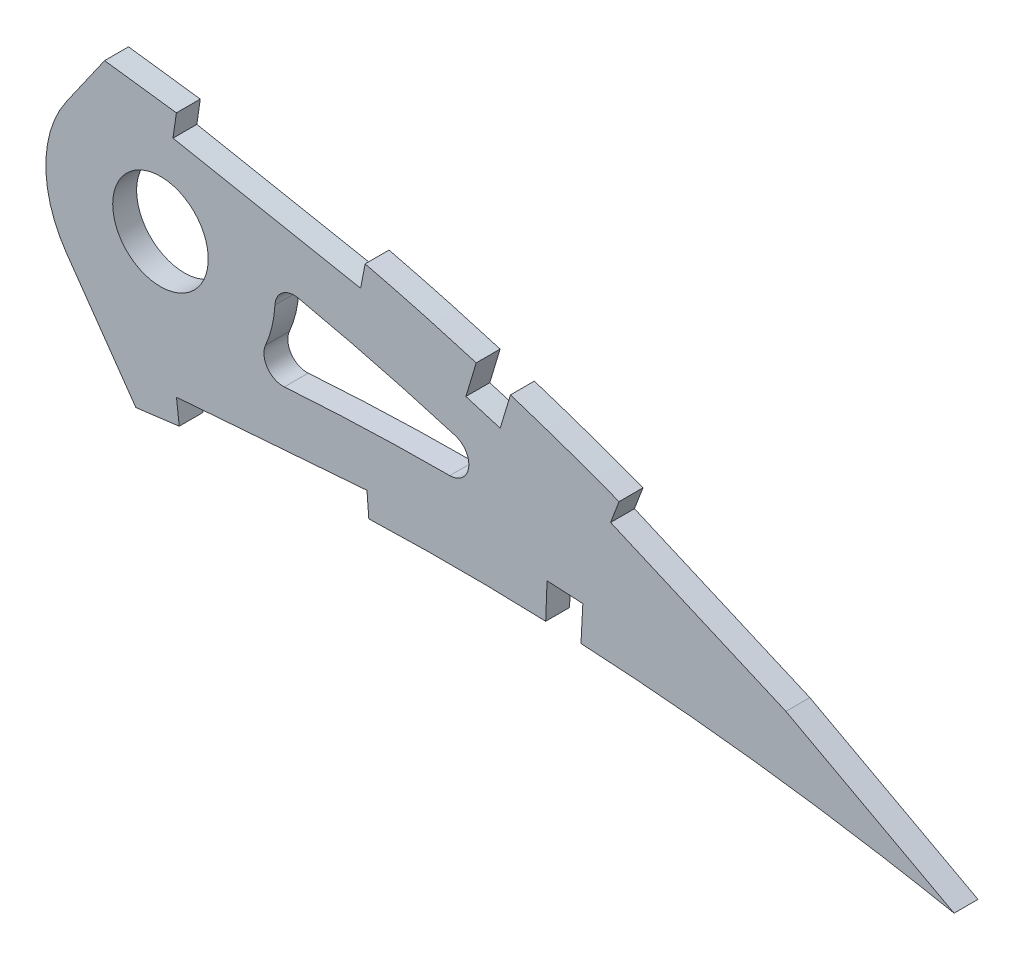
SolidWorks part; units mm, degrees
ref_plane "Front Plane" through (0, 0, 0) normal (0, 0, 1) x (1, 0, 0)
ref_plane "Top Plane" through (0, 0, 0) normal (0, 1, 0) x (1, 0, 0)
ref_plane "Right Plane" through (0, 0, 0) normal (1, 0, 0) x (0, 0, -1)
curve "Curve1"
  spline degree 3 poles (383.949, 0.5986, 0) (383.9196, 0.6168, 0) (383.802, 0.6894, 0) (383.5372, 0.8518, 0) (383.0962, 1.1224, 0) (382.4788, 1.4992, 0) (381.6856, 1.9812, 0) (380.716, 2.5651, 0) (379.5708, 3.249, 0) (378.2502, 4.0295, 0) (376.7543, 4.9032, 0) (375.0838, 5.8664, 0) (373.2387, 6.9137, 0) (371.2197, 8.0407, 0) (369.0276, 9.2423, 0) (366.6628, 10.5128, 0) (364.1261, 11.8459, 0) (361.4185, 13.2358, 0) (358.5405, 14.6749, 0) (355.4934, 16.1571, 0) (352.2782, 17.675, 0) (348.8962, 19.2207, 0) (345.3491, 20.7877, 0) (341.638, 22.3663, 0) (337.765, 23.9497, 0) (333.7318, 25.5289, 0) (329.5407, 27.0966, 0) (325.1933, 28.6428, 0) (320.6929, 30.1607, 0) (316.0417, 31.6403, 0) (311.2431, 33.0737, 0) (306.2997, 34.4516, 0) (301.2157, 35.767, 0) (295.9944, 37.0101, 0) (290.6401, 38.1728, 0) (285.1572, 39.2479, 0) (279.5502, 40.2249, 0) (273.8346, 41.1028, 0) (268.1025, 41.8331, 0) (262.3821, 42.5494, 0) (256.6703, 43.2222, 0) (250.8886, 43.8666, 0) (245.0428, 44.4788, 0) (239.1384, 45.057, 0) (233.1816, 45.5987, 0) (227.1785, 46.1022, 0) (221.135, 46.5647, 0) (215.0573, 46.9856, 0) (208.9515, 47.361, 0) (202.8242, 47.6908, 0) (196.6815, 47.9725, 0) (190.5298, 48.2044, 0) (184.3757, 48.385, 0) (178.2255, 48.5125, 0) (172.0859, 48.5861, 0) (165.9633, 48.6039, 0) (159.8643, 48.5655, 0) (153.7954, 48.4696, 0) (147.7632, 48.3149, 0) (141.7741, 48.1011, 0) (135.8345, 47.8283, 0) (129.951, 47.4942, 0) (124.1299, 47.1009, 0) (118.3778, 46.6469, 0) (112.701, 46.1319, 0) (107.1053, 45.5581, 0) (101.5971, 44.9239, 0) (96.1822, 44.2312, 0) (90.8666, 43.4813, 0) (85.6562, 42.6738, 0) (80.5566, 41.8111, 0) (75.5733, 40.894, 0) (70.7116, 39.9252, 0) (65.9768, 38.9049, 0) (61.3739, 37.8363, 0) (56.9076, 36.7211, 0) (52.5828, 35.5615, 0) (48.4038, 34.3602, 0) (44.375, 33.1199, 0) (40.5009, 31.842, 0) (36.7845, 30.5314, 0) (33.2304, 29.1889, 0) (29.8413, 27.8188, 0) (26.6212, 26.4228, 0) (23.5724, 25.0052, 0) (20.6984, 23.5677, 0) (18.0014, 22.1143, 0) (15.4839, 20.6472, 0) (13.1483, 19.1691, 0) (10.9958, 17.6837, 0) (9.0293, 16.1921, 0) (7.2493, 14.698, 0) (5.6571, 13.2036, 0) (4.255, 11.71, 0) (3.0428, 10.2198, 0) (2.0222, 8.7343, 0) (1.1933, 7.2547, 0) (0.558, 5.7822, 0) (0.1157, 4.3176, 0) (-0.1263, 2.863, 0) (-0.1866, 1.4174, 0) (-0.0621, 0.4718, 0) (0, 0, 0) knots 0 0 0 0 0.000254 0.001015 0.002283 0.004057 0.006331 0.009105 0.012374 0.016134 0.02038 0.025106 0.030306 0.035972 0.0421 0.048678 0.055702 0.06316 0.071046 0.07935 0.088063 0.097176 0.106678 0.116562 0.126814 0.137428 0.148394 0.1597 0.171338 0.183298 0.19557 0.208144 0.221012 0.234162 0.247587 0.261277 0.275223 0.289414 0.303771 0.317689 0.331784 0.34604 0.360444 0.374983 0.38964 0.404403 0.419257 0.434187 0.449177 0.464215 0.479284 0.49437 0.509458 0.524532 0.539579 0.554583 0.56953 0.584403 0.599191 0.613877 0.628447 0.642889 0.657186 0.671326 0.685294 0.699078 0.712665 0.726043 0.739198 0.752118 0.764792 0.777208 0.789356 0.801224 0.812804 0.824083 0.835055 0.84571 0.856038 0.866034 0.875689 0.884998 0.893953 0.902553 0.910789 0.918661 0.926166 0.933303 0.940071 0.946475 0.952518 0.958205 0.963547 0.968557 0.97325 0.977651 0.981787 0.985694 0.989415 0.993001 0.996508 1 1 1 1
curve "Curve2"
  spline degree 3 poles (0, 0, 0) (0.0986, -0.4654, 0) (0.2962, -1.3985, 0) (0.8332, -2.7416, 0) (1.5434, -4.0328, 0) (2.4415, -5.2686, 0) (3.5218, -6.4485, 0) (4.7818, -7.574, 0) (6.2202, -8.6443, 0) (7.8352, -9.659, 0) (9.6244, -10.6191, 0) (11.5859, -11.5241, 0) (13.7178, -12.3737, 0) (16.0178, -13.1667, 0) (18.4831, -13.9043, 0) (21.1113, -14.5848, 0) (23.8995, -15.2091, 0) (26.845, -15.7756, 0) (29.9446, -16.2848, 0) (33.195, -16.7366, 0) (36.593, -17.1311, 0) (40.1351, -17.4676, 0) (43.8179, -17.7467, 0) (47.6377, -17.9687, 0) (51.5909, -18.1343, 0) (55.6735, -18.2428, 0) (59.8817, -18.2959, 0) (64.2115, -18.2945, 0) (68.6589, -18.238, 0) (73.2199, -18.1297, 0) (77.8902, -17.9689, 0) (82.6657, -17.7575, 0) (87.5419, -17.4976, 0) (92.5144, -17.1902, 0) (97.5791, -16.8365, 0) (102.7313, -16.4394, 0) (107.9665, -16, 0) (113.2801, -15.5207, 0) (118.6674, -15.0039, 0) (124.1237, -14.4514, 0) (129.6442, -13.8657, 0) (135.2241, -13.2487, 0) (140.8584, -12.6036, 0) (146.5422, -11.9317, 0) (152.2705, -11.2369, 0) (158.0381, -10.5203, 0) (163.84, -9.7848, 0) (169.6711, -9.0339, 0) (175.5259, -8.2674, 0) (181.3995, -7.4908, 0) (187.2862, -6.7036, 0) (193.1809, -5.9096, 0) (199.0781, -5.1115, 0) (204.9721, -4.3094, 0) (210.8578, -3.5066, 0) (216.7295, -2.7054, 0) (222.5817, -1.9059, 0) (228.409, -1.112, 0) (234.2055, -0.3236, 0) (239.9659, 0.4577, 0) (245.6847, 1.2295, 0) (251.3565, 1.9909, 0) (256.9754, 2.7413, 0) (262.5357, 3.4812, 0) (267.9487, 4.188, 0) (273.2002, 4.8993, 0) (278.3079, 5.4825, 0) (283.3519, 5.9802, 0) (288.3377, 6.3883, 0) (293.259, 6.7125, 0) (298.1104, 6.9553, 0) (302.886, 7.1201, 0) (307.5799, 7.2116, 0) (312.186, 7.2323, 0) (316.6983, 7.1886, 0) (321.1107, 7.0842, 0) (325.4171, 6.9238, 0) (329.6115, 6.7126, 0) (333.688, 6.4566, 0) (337.6405, 6.1594, 0) (341.4634, 5.828, 0) (345.1508, 5.4673, 0) (348.6971, 5.0813, 0) (352.0971, 4.6782, 0) (355.3453, 4.2606, 0) (358.4369, 3.8354, 0) (361.3669, 3.4069, 0) (364.1307, 2.9806, 0) (366.7239, 2.5605, 0) (369.1422, 2.1521, 0) (371.3821, 1.7594, 0) (373.4394, 1.3862, 0) (375.3115, 1.0371, 0) (376.9946, 0.7139, 0) (378.4864, 0.4219, 0) (379.7842, 0.1625, 0) (380.886, -0.0608, 0) (381.79, -0.247, 0) (382.4947, -0.3932, 0) (382.9989, -0.4995, 0) (383.3019, -0.5627, 0) (383.4365, -0.5914, 0) (383.4701, -0.5986, 0) knots 0 0 0 0 0.003638 0.007293 0.011028 0.014901 0.018963 0.023258 0.027821 0.032679 0.037853 0.043362 0.049215 0.055422 0.061989 0.068918 0.076211 0.083868 0.091887 0.100266 0.109 0.118085 0.127515 0.137285 0.147388 0.157816 0.168563 0.179619 0.190977 0.202627 0.21456 0.226767 0.239236 0.251959 0.264924 0.27812 0.291536 0.30516 0.318981 0.332985 0.347163 0.361499 0.375981 0.390597 0.405333 0.420175 0.43511 0.450124 0.465203 0.480333 0.495501 0.51069 0.525887 0.541078 0.556247 0.571382 0.586466 0.601485 0.616424 0.631269 0.646007 0.660621 0.675098 0.689423 0.703582 0.716908 0.730009 0.742952 0.755726 0.76832 0.780724 0.792927 0.804916 0.816679 0.828204 0.839475 0.850481 0.861208 0.871639 0.881763 0.891564 0.901027 0.910139 0.918884 0.927249 0.935221 0.942785 0.949928 0.956638 0.962904 0.968712 0.974054 0.978918 0.983297 0.98718 0.990561 0.993433 0.995791 0.99763 0.998946 0.999737 1 1 1 1
sketch "Sketch1" plane through (0, 0, 0) normal (0, 0, 1) x (1, 0, 0)
  line L23 (383.4597, -0.5986) -> (387.1511, -1.386)
  line L24 (383.9386, 0.5986) -> (387.1511, -1.386)
  spline S4 degree 3 poles (0, 0) (0.0986, -0.4654) (0.2962, -1.3984) (0.8332, -2.7416) (1.5433, -4.0327) (2.4415, -5.2684) (3.5217, -6.4484) (4.7816, -7.5738) (6.22, -8.6441) (7.835, -9.6587) (9.6242, -10.6188) (11.5856, -11.5238) (13.7174, -12.3733) (16.0173, -13.1663) (18.4826, -13.9039) (21.1108, -14.5844) (23.8989, -15.2087) (26.8443, -15.7751) (29.9438, -16.2844) (33.1941, -16.7361) (36.592, -17.1306) (40.134, -17.4671) (43.8167, -17.7462) (47.6365, -17.9682) (51.5895, -18.1338) (55.672, -18.2423) (59.88, -18.2954) (64.2098, -18.294) (68.657, -18.2375) (73.2179, -18.1293) (77.8881, -17.9684) (82.6634, -17.757) (87.5395, -17.4972) (92.5119, -17.1897) (97.5764, -16.836) (102.7286, -16.439) (107.9636, -15.9995) (113.2771, -15.5202) (118.6642, -15.0035) (124.1204, -14.451) (129.6407, -13.8653) (135.2204, -13.2483) (140.8546, -12.6033) (146.5382, -11.9314) (152.2664, -11.2365) (158.0338, -10.52) (163.8356, -9.7845) (169.6665, -9.0336) (175.5212, -8.2672) (181.3946, -7.4906) (187.2811, -6.7034) (193.1757, -5.9095) (199.0727, -5.1113) (204.9666, -4.3092) (210.8521, -3.5065) (216.7237, -2.7054) (222.5757, -1.9059) (228.4028, -1.112) (234.1992, -0.3236) (239.9594, 0.4576) (245.6781, 1.2294) (251.3497, 1.9908) (256.9684, 2.7413) (262.5286, 3.4811) (267.9415, 4.1879) (273.1928, 4.8992) (278.3003, 5.4823) (283.3443, 5.98) (288.3299, 6.3881) (293.2511, 6.7123) (298.1023, 6.9552) (302.8778, 7.1199) (307.5715, 7.2114) (312.1776, 7.2321) (316.6897, 7.1884) (321.102, 7.084) (325.4083, 6.9236) (329.6026, 6.7124) (333.679, 6.4564) (337.6313, 6.1592) (341.4541, 5.8278) (345.1414, 5.4671) (348.6876, 5.0812) (352.0875, 4.6781) (355.3357, 4.2605) (358.4272, 3.8353) (361.3571, 3.4068) (364.1208, 2.9805) (366.7139, 2.5604) (369.1322, 2.1521) (371.372, 1.7594) (373.4293, 1.3862) (375.3013, 1.0371) (376.9844, 0.7139) (378.4761, 0.4219) (379.7739, 0.1625) (380.8757, -0.0608) (381.7796, -0.247) (382.4844, -0.3932) (382.9885, -0.4994) (383.2915, -0.5627) (383.4261, -0.5914) (383.4597, -0.5986) knots 0 0 0 0 0.003638 0.007293 0.011028 0.014901 0.018963 0.023258 0.027821 0.032679 0.037853 0.043362 0.049215 0.055422 0.061989 0.068918 0.076211 0.083868 0.091887 0.100266 0.109 0.118085 0.127515 0.137285 0.147388 0.157816 0.168563 0.179619 0.190977 0.202627 0.21456 0.226767 0.239236 0.251959 0.264924 0.27812 0.291536 0.30516 0.318981 0.332985 0.347163 0.361499 0.375981 0.390597 0.405333 0.420175 0.43511 0.450124 0.465203 0.480333 0.495501 0.51069 0.525887 0.541078 0.556247 0.571382 0.586466 0.601485 0.616424 0.631269 0.646007 0.660621 0.675098 0.689423 0.703582 0.716908 0.730009 0.742952 0.755726 0.76832 0.780724 0.792927 0.804916 0.816679 0.828204 0.839475 0.850481 0.861208 0.871639 0.881763 0.891564 0.901027 0.910139 0.918884 0.927249 0.935221 0.942785 0.949928 0.956638 0.962904 0.968712 0.974054 0.978918 0.983297 0.98718 0.990561 0.993433 0.995791 0.99763 0.998946 0.999737 1 1 1 1
  spline S5 degree 3 poles (383.9386, 0.5986) (383.9092, 0.6167) (383.7916, 0.6893) (383.5268, 0.8518) (383.0858, 1.1223) (382.4685, 1.4991) (381.6752, 1.9811) (380.7057, 2.565) (379.5606, 3.2489) (378.24, 4.0294) (376.7441, 4.9031) (375.0736, 5.8662) (373.2286, 6.9135) (371.2097, 8.0405) (369.0176, 9.242) (366.6529, 10.5125) (364.1162, 11.8456) (361.4087, 13.2354) (358.5307, 14.6745) (355.4837, 16.1566) (352.2687, 17.6745) (348.8867, 19.2201) (345.3398, 20.7871) (341.6288, 22.3657) (337.7559, 23.949) (333.7228, 25.5282) (329.5317, 27.0959) (325.1845, 28.642) (320.6843, 30.1598) (316.0332, 31.6395) (311.2346, 33.0728) (306.2914, 34.4507) (301.2076, 35.766) (295.9864, 37.0091) (290.6322, 38.1717) (285.1495, 39.2469) (279.5426, 40.2238) (273.8272, 41.1017) (268.0952, 41.832) (262.375, 42.5482) (256.6633, 43.2211) (250.8818, 43.8654) (245.0361, 44.4776) (239.1319, 45.0558) (233.1753, 45.5974) (227.1724, 46.1009) (221.129, 46.5635) (215.0515, 46.9843) (208.9459, 47.3597) (202.8187, 47.6895) (196.6762, 47.9712) (190.5246, 48.2031) (184.3707, 48.3836) (178.2206, 48.5111) (172.0812, 48.5848) (165.9588, 48.6026) (159.86, 48.5642) (153.7912, 48.4683) (147.7592, 48.3136) (141.7702, 48.0998) (135.8308, 47.827) (129.9475, 47.4929) (124.1266, 47.0997) (118.3746, 46.6456) (112.6979, 46.1306) (107.1024, 45.5568) (101.5944, 44.9227) (96.1796, 44.23) (90.8641, 43.4801) (85.6539, 42.6727) (80.5544, 41.81) (75.5713, 40.8929) (70.7097, 39.9241) (65.975, 38.9039) (61.3722, 37.8353) (56.906, 36.7201) (52.5814, 35.5606) (48.4025, 34.3593) (44.3738, 33.119) (40.4998, 31.8412) (36.7835, 30.5306) (33.2295, 29.1881) (29.8405, 27.818) (26.6204, 26.4221) (23.5718, 25.0045) (20.6979, 23.5671) (18.0009, 22.1137) (15.4834, 20.6466) (13.148, 19.1685) (10.9955, 17.6833) (9.029, 16.1917) (7.2491, 14.6976) (5.657, 13.2033) (4.2548, 11.7097) (3.0427, 10.2196) (2.0221, 8.734) (1.1932, 7.2545) (0.558, 5.782) (0.1157, 4.3174) (-0.1263, 2.8629) (-0.1866, 1.4173) (-0.0621, 0.4717) (0, 0) knots 0 0 0 0 0.000254 0.001015 0.002283 0.004057 0.006331 0.009105 0.012374 0.016134 0.02038 0.025106 0.030306 0.035972 0.0421 0.048678 0.055702 0.06316 0.071046 0.07935 0.088063 0.097176 0.106678 0.116562 0.126814 0.137428 0.148394 0.1597 0.171338 0.183298 0.19557 0.208144 0.221012 0.234162 0.247587 0.261277 0.275223 0.289414 0.303771 0.317689 0.331784 0.34604 0.360444 0.374983 0.38964 0.404403 0.419257 0.434187 0.449177 0.464215 0.479284 0.49437 0.509458 0.524532 0.539579 0.554583 0.56953 0.584403 0.599191 0.613877 0.628447 0.642889 0.657186 0.671326 0.685294 0.699078 0.712665 0.726043 0.739198 0.752118 0.764792 0.777208 0.789356 0.801224 0.812804 0.824083 0.835055 0.84571 0.856038 0.866034 0.875689 0.884998 0.893953 0.902553 0.910789 0.918661 0.926166 0.933303 0.940071 0.946475 0.952518 0.958205 0.963547 0.968557 0.97325 0.977651 0.981787 0.985694 0.989415 0.993001 0.996508 1 1 1 1
extrude "Boss-Extrude1" add sketch "Sketch1" along normal blind 3.175
sketch "Sketch3" plane through (0, 0, 0) normal (0, 0, -1) x (-1, 0, 0)
  circle A1 centre (-272.4199, 26.2554) radius 6.35
extrude "Cut-Extrude2" cut sketch "Sketch3" against normal blind 7.62
sketch "Sketch4" plane through (0, 0, 3.175) normal (0, 0, 1) x (1, 0, 0)
  line L0 (272.4199, 26.2554) -> (275.6183, 26.2554)
  line L1 (259.936, 34.9967) -> (264.9932, 42.2191)
  line L2 (259.936, 17.5141) -> (269.1511, 4.3535)
  circle A0 centre (272.4199, 26.2554) radius 6.35 construction
  circle A1 centre (272.4199, 26.2554) radius 6.35
  circle A2 centre (272.4199, 26.2554) radius 15.24
  spline S0 degree 3 poles (-2900.5811, -762.1564) (60.7171, 58.1372) (-7.1311, 17.1797) (0.8332, -2.7416) (1.5433, -4.0327) (2.4415, -5.2684) (3.5217, -6.4484) (4.7816, -7.5738) (6.22, -8.6441) (7.835, -9.6587) (9.6242, -10.6188) (11.5856, -11.5238) (13.7174, -12.3733) (16.0173, -13.1663) (18.4826, -13.9039) (21.1108, -14.5844) (23.8989, -15.2087) (26.8443, -15.7751) (29.9438, -16.2844) (33.1941, -16.7361) (36.592, -17.1306) (40.134, -17.4671) (43.8167, -17.7462) (47.6365, -17.9682) (51.5895, -18.1338) (55.672, -18.2423) (59.88, -18.2954) (64.2098, -18.294) (68.657, -18.2375) (73.2179, -18.1293) (77.8881, -17.9684) (82.6634, -17.757) (87.5395, -17.4972) (92.5119, -17.1897) (97.5764, -16.836) (102.7286, -16.439) (107.9636, -15.9995) (113.2771, -15.5202) (118.6642, -15.0035) (124.1204, -14.451) (129.6407, -13.8653) (135.2204, -13.2483) (140.8546, -12.6033) (146.5382, -11.9314) (152.2664, -11.2365) (158.0338, -10.52) (163.8356, -9.7845) (169.6665, -9.0336) (175.5212, -8.2672) (181.3946, -7.4906) (187.2811, -6.7034) (193.1757, -5.9095) (199.0727, -5.1113) (204.9666, -4.3092) (210.8521, -3.5065) (216.7237, -2.7054) (222.5757, -1.9059) (228.4028, -1.112) (234.1992, -0.3236) (239.9594, 0.4576) (245.6781, 1.2294) (251.3497, 1.9908) (256.9684, 2.7413) (262.5286, 3.4811) (267.9415, 4.1879) (273.1928, 4.8992) (278.3003, 5.4823) (283.3443, 5.98) (288.3299, 6.3881) (293.2511, 6.7123) (298.1023, 6.9552) (302.8778, 7.1199) (307.5715, 7.2114) (312.1776, 7.2321) (316.6897, 7.1884) (321.102, 7.084) (325.4083, 6.9236) (329.6026, 6.7124) (333.679, 6.4564) (337.6313, 6.1592) (341.4541, 5.8278) (345.1414, 5.4671) (348.6876, 5.0812) (352.0875, 4.6781) (355.3357, 4.2605) (358.4272, 3.8353) (361.3571, 3.4068) (364.1208, 2.9805) (366.7139, 2.5604) (369.1322, 2.1521) (371.372, 1.7594) (373.4293, 1.3862) (375.3013, 1.0371) (376.9844, 0.7139) (378.4761, 0.4219) (379.7739, 0.1625) (380.8757, -0.0608) (381.7796, -0.247) (382.4844, -0.3932) (382.9885, -0.4994) (397.7614, -3.5828) (410.8952, -13.5854) (1047.3532, 2924.2375) knots -0.152541 -0.152541 -0.152541 -0.152541 0.003638 0.007293 0.011028 0.014901 0.018963 0.023258 0.027821 0.032679 0.037853 0.043362 0.049215 0.055422 0.061989 0.068918 0.076211 0.083868 0.091887 0.100266 0.109 0.118085 0.127515 0.137285 0.147388 0.157816 0.168563 0.179619 0.190977 0.202627 0.21456 0.226767 0.239236 0.251959 0.264924 0.27812 0.291536 0.30516 0.318981 0.332985 0.347163 0.361499 0.375981 0.390597 0.405333 0.420175 0.43511 0.450124 0.465203 0.480333 0.495501 0.51069 0.525887 0.541078 0.556247 0.571382 0.586466 0.601485 0.616424 0.631269 0.646007 0.660621 0.675098 0.689423 0.703582 0.716908 0.730009 0.742952 0.755726 0.76832 0.780724 0.792927 0.804916 0.816679 0.828204 0.839475 0.850481 0.861208 0.871639 0.881763 0.891564 0.901027 0.910139 0.918884 0.927249 0.935221 0.942785 0.949928 0.956638 0.962904 0.968712 0.974054 0.978918 0.983297 0.98718 0.990561 0.993433 0.995791 0.99763 0.998946 0.999737 1.113214 1.113214 1.113214 1.113214 only from (0, 0) to (383.4597, -0.5986) construction
  spline S1 degree 3 poles (1998.8466, 2527.3991) (408.7537, -22.1004) (397.8856, -7.9557) (383.5268, 0.8518) (383.0858, 1.1223) (382.4685, 1.4991) (381.6752, 1.9811) (380.7057, 2.565) (379.5606, 3.2489) (378.24, 4.0294) (376.7441, 4.9031) (375.0736, 5.8662) (373.2286, 6.9135) (371.2097, 8.0405) (369.0176, 9.242) (366.6529, 10.5125) (364.1162, 11.8456) (361.4087, 13.2354) (358.5307, 14.6745) (355.4837, 16.1566) (352.2687, 17.6745) (348.8867, 19.2201) (345.3398, 20.7871) (341.6288, 22.3657) (337.7559, 23.949) (333.7228, 25.5282) (329.5317, 27.0959) (325.1845, 28.642) (320.6843, 30.1598) (316.0332, 31.6395) (311.2346, 33.0728) (306.2914, 34.4507) (301.2076, 35.766) (295.9864, 37.0091) (290.6322, 38.1717) (285.1495, 39.2469) (279.5426, 40.2238) (273.8272, 41.1017) (268.0952, 41.832) (262.375, 42.5482) (256.6633, 43.2211) (250.8818, 43.8654) (245.0361, 44.4776) (239.1319, 45.0558) (233.1753, 45.5974) (227.1724, 46.1009) (221.129, 46.5635) (215.0515, 46.9843) (208.9459, 47.3597) (202.8187, 47.6895) (196.6762, 47.9712) (190.5246, 48.2031) (184.3707, 48.3836) (178.2206, 48.5111) (172.0812, 48.5848) (165.9588, 48.6026) (159.86, 48.5642) (153.7912, 48.4683) (147.7592, 48.3136) (141.7702, 48.0998) (135.8308, 47.827) (129.9475, 47.4929) (124.1266, 47.0997) (118.3746, 46.6456) (112.6979, 46.1306) (107.1024, 45.5568) (101.5944, 44.9227) (96.1796, 44.23) (90.8641, 43.4801) (85.6539, 42.6727) (80.5544, 41.81) (75.5713, 40.8929) (70.7097, 39.9241) (65.975, 38.9039) (61.3722, 37.8353) (56.906, 36.7201) (52.5814, 35.5606) (48.4025, 34.3593) (44.3738, 33.119) (40.4998, 31.8412) (36.7835, 30.5306) (33.2295, 29.1881) (29.8405, 27.818) (26.6204, 26.4221) (23.5718, 25.0045) (20.6979, 23.5671) (18.0009, 22.1137) (15.4834, 20.6466) (13.148, 19.1685) (10.9955, 17.6833) (9.029, 16.1917) (7.2491, 14.6976) (5.657, 13.2033) (4.2548, 11.7097) (3.0427, 10.2196) (2.0221, 8.734) (1.1932, 7.2545) (0.558, 5.782) (0.1157, 4.3174) (-0.1263, 2.8629) (-1.0184, -18.5368) (76.7539, -34.5403) (-2989.0976, -246.1964) knots -0.121519 -0.121519 -0.121519 -0.121519 0.000254 0.001015 0.002283 0.004057 0.006331 0.009105 0.012374 0.016134 0.02038 0.025106 0.030306 0.035972 0.0421 0.048678 0.055702 0.06316 0.071046 0.07935 0.088063 0.097176 0.106678 0.116562 0.126814 0.137428 0.148394 0.1597 0.171338 0.183298 0.19557 0.208144 0.221012 0.234162 0.247587 0.261277 0.275223 0.289414 0.303771 0.317689 0.331784 0.34604 0.360444 0.374983 0.38964 0.404403 0.419257 0.434187 0.449177 0.464215 0.479284 0.49437 0.509458 0.524532 0.539579 0.554583 0.56953 0.584403 0.599191 0.613877 0.628447 0.642889 0.657186 0.671326 0.685294 0.699078 0.712665 0.726043 0.739198 0.752118 0.764792 0.777208 0.789356 0.801224 0.812804 0.824083 0.835055 0.84571 0.856038 0.866034 0.875689 0.884998 0.893953 0.902553 0.910789 0.918661 0.926166 0.933303 0.940071 0.946475 0.952518 0.958205 0.963547 0.968557 0.97325 0.977651 0.981787 0.985694 0.989415 0.993001 0.996508 1.146107 1.146107 1.146107 1.146107 only from (383.9386, 0.5986) to (0, 0) construction
  spline S2 degree 3 poles (161.4571, -10.0855) (162.2464, -9.9853) (164.9804, -9.6371) (169.6665, -9.0336) (175.5212, -8.2672) (181.3946, -7.4906) (187.2811, -6.7034) (193.1757, -5.9095) (199.0727, -5.1113) (204.9666, -4.3092) (210.8521, -3.5065) (216.7237, -2.7054) (222.5757, -1.9059) (228.4028, -1.112) (234.1992, -0.3236) (239.9594, 0.4576) (245.6781, 1.2294) (251.3497, 1.9908) (256.9684, 2.7413) (262.5286, 3.4811) (267.9415, 4.1879) (273.1928, 4.8992) (278.3003, 5.4823) (283.3443, 5.98) (288.3299, 6.3881) (293.2511, 6.7123) (298.1023, 6.9552) (302.8778, 7.1199) (307.5715, 7.2114) (312.1776, 7.2321) (316.6897, 7.1884) (321.102, 7.084) (325.4083, 6.9236) (329.6026, 6.7124) (333.679, 6.4564) (337.6313, 6.1592) (341.4541, 5.8278) (345.1414, 5.4671) (348.6876, 5.0812) (352.0875, 4.6781) (355.3357, 4.2605) (358.4272, 3.8353) (361.3571, 3.4068) (364.1208, 2.9805) (366.7139, 2.5604) (369.1322, 2.1521) (371.372, 1.7594) (373.4293, 1.3862) (375.3013, 1.0371) (376.9844, 0.7139) (378.4761, 0.4219) (379.7739, 0.1625) (380.8757, -0.0608) (381.7796, -0.247) (382.4844, -0.3932) (382.9885, -0.4994) (383.2915, -0.5627) (383.4261, -0.5914) (383.4597, -0.5986) knots 0.429016 0.429016 0.429016 0.429016 0.43511 0.450124 0.465203 0.480333 0.495501 0.51069 0.525887 0.541078 0.556247 0.571382 0.586466 0.601485 0.616424 0.631269 0.646007 0.660621 0.675098 0.689423 0.703582 0.716908 0.730009 0.742952 0.755726 0.76832 0.780724 0.792927 0.804916 0.816679 0.828204 0.839475 0.850481 0.861208 0.871639 0.881763 0.891564 0.901027 0.910139 0.918884 0.927249 0.935221 0.942785 0.949928 0.956638 0.962904 0.968712 0.974054 0.978918 0.983297 0.98718 0.990561 0.993433 0.995791 0.99763 0.998946 0.999737 1 1 1 1
  spline S3 degree 3 poles (383.9386, 0.5986) (383.9092, 0.6167) (383.7916, 0.6893) (383.5268, 0.8518) (383.0858, 1.1223) (382.4685, 1.4991) (381.6752, 1.9811) (380.7057, 2.565) (379.5606, 3.2489) (378.24, 4.0294) (376.7441, 4.9031) (375.0736, 5.8662) (373.2286, 6.9135) (371.2097, 8.0405) (369.0176, 9.242) (366.6529, 10.5125) (364.1162, 11.8456) (361.4087, 13.2354) (358.5307, 14.6745) (355.4837, 16.1566) (352.2687, 17.6745) (348.8867, 19.2201) (345.3398, 20.7871) (341.6288, 22.3657) (337.7559, 23.949) (333.7228, 25.5282) (329.5317, 27.0959) (325.1845, 28.642) (320.6843, 30.1598) (316.0332, 31.6395) (311.2346, 33.0728) (306.2914, 34.4507) (301.2076, 35.766) (295.9864, 37.0091) (290.6322, 38.1717) (285.1495, 39.2469) (279.5426, 40.2238) (273.8272, 41.1017) (268.0952, 41.832) (262.375, 42.5482) (256.6633, 43.2211) (250.8818, 43.8654) (245.0361, 44.4776) (239.1319, 45.0558) (233.1753, 45.5974) (227.1724, 46.1009) (221.129, 46.5635) (215.0515, 46.9843) (208.9459, 47.3597) (202.8187, 47.6895) (196.6762, 47.9712) (190.5246, 48.2031) (184.3707, 48.3836) (178.2206, 48.5111) (172.0812, 48.5848) (165.9588, 48.6026) (159.86, 48.5642) (153.5038, 48.4638) (149.182, 48.3499) (146.8838, 48.276) knots 0 0 0 0 0.000254 0.001015 0.002283 0.004057 0.006331 0.009105 0.012374 0.016134 0.02038 0.025106 0.030306 0.035972 0.0421 0.048678 0.055702 0.06316 0.071046 0.07935 0.088063 0.097176 0.106678 0.116562 0.126814 0.137428 0.148394 0.1597 0.171338 0.183298 0.19557 0.208144 0.221012 0.234162 0.247587 0.261277 0.275223 0.289414 0.303771 0.317689 0.331784 0.34604 0.360444 0.374983 0.38964 0.404403 0.419257 0.434187 0.449177 0.464215 0.479284 0.49437 0.509458 0.524532 0.539579 0.554583 0.56953 0.584403 0.601304 0.601304 0.601304 0.601304
  spline S4 degree 1 poles (378.5989, -8.0451) (147.21, 38.1213) knots 0 0 1 1 construction
  spline S5 degree 3 poles (378.5989, -8.0451) (378.472, -7.9667) (378.2234, -7.8142) (377.6805, -7.4812) (376.7611, -6.9205) (374.9109, -5.8032) (371.1788, -3.5966) (363.6516, 0.6712) (348.2892, 8.639) (330.0962, 16.359) (311.3792, 22.5636) (297.107, 26.4342) (285.0856, 28.9814) (276.5539, 30.4164) (271.7323, 31.12) (268.0333, 31.5987) (264.2273, 32.0776) (259.2208, 32.6948) (250.4292, 33.7129) (237.8617, 35.009) (222.7587, 36.2937) (202.6061, 37.6338) (177.3909, 38.5745) (157.2697, 38.4445) (147.21, 38.1213) knots 0 0 0 0 0.001174 0.002349 0.004698 0.009395 0.018791 0.037581 0.075163 0.150326 0.187907 0.225489 0.26307 0.281861 0.291256 0.300652 0.310047 0.319443 0.338233 0.375815 0.413396 0.450978 0.526141 0.601304 0.601304 0.601304 0.601304
  spline S6 degree 1 poles (160.178, -0.0063) (385.5793, 9.3379) knots 0 0 1 1 construction
  spline S7 degree 3 poles (160.178, -0.0063) (169.3975, 1.1637) (187.8091, 3.6001) (210.885, 6.7523) (229.3545, 9.2731) (243.2292, 11.1537) (254.7583, 12.7013) (262.905, 13.7751) (267.4672, 14.3775) (270.981, 14.8497) (274.6098, 15.2908) (279.3773, 15.8089) (285.3756, 16.3645) (292.5728, 16.8641) (302.1885, 17.3159) (314.2133, 17.4755) (333.4344, 16.8874) (352.5648, 15.0706) (369.1185, 12.5101) (377.3698, 10.9967) (381.4564, 10.1902) (383.3728, 9.7984) (384.2388, 9.6192) (384.6955, 9.524) (385.0455, 9.4502) (385.329, 9.391) (385.4982, 9.3552) (385.5793, 9.3379) knots 0.429016 0.429016 0.429016 0.429016 0.500389 0.571762 0.607448 0.643135 0.678821 0.696665 0.705586 0.714508 0.723429 0.732351 0.750194 0.768038 0.785881 0.821567 0.857254 0.928627 0.964313 0.982157 0.991078 0.995539 0.996654 0.99777 0.998885 0.999442 1 1 1 1
  spline M7 degree 3 poles (383.9386, 0.5986) (383.9092, 0.6167) (383.7916, 0.6893) (383.5268, 0.8518) (383.0858, 1.1223) (382.4685, 1.4991) (381.6752, 1.9811) (380.7057, 2.565) (379.5606, 3.2489) (378.24, 4.0294) (376.7441, 4.9031) (375.0736, 5.8662) (373.2286, 6.9135) (371.2097, 8.0405) (369.0176, 9.242) (366.6529, 10.5125) (364.1162, 11.8456) (361.4087, 13.2354) (358.5307, 14.6745) (355.4837, 16.1566) (352.2687, 17.6745) (348.8867, 19.2201) (345.3398, 20.7871) (341.6288, 22.3657) (337.7559, 23.949) (333.7228, 25.5282) (329.5317, 27.0959) (325.1845, 28.642) (320.6843, 30.1598) (316.0332, 31.6395) (311.2346, 33.0728) (306.2914, 34.4507) (301.2076, 35.766) (295.9864, 37.0091) (290.6322, 38.1717) (285.1495, 39.2469) (279.5426, 40.2238) (273.8272, 41.1017) (268.0952, 41.832) (262.375, 42.5482) (256.6633, 43.2211) (250.8818, 43.8654) (245.0361, 44.4776) (239.1319, 45.0558) (233.1753, 45.5974) (227.1724, 46.1009) (221.129, 46.5635) (215.0515, 46.9843) (208.9459, 47.3597) (202.8187, 47.6895) (196.6762, 47.9712) (190.5246, 48.2031) (184.3707, 48.3836) (178.2206, 48.5111) (172.0812, 48.5848) (165.9588, 48.6026) (159.86, 48.5642) (153.7912, 48.4683) (147.7592, 48.3136) (141.7702, 48.0998) (135.8308, 47.827) (129.9475, 47.4929) (124.1266, 47.0997) (118.3746, 46.6456) (112.6979, 46.1306) (107.1024, 45.5568) (101.5944, 44.9227) (96.1796, 44.23) (90.8641, 43.4801) (85.6539, 42.6727) (80.5544, 41.81) (75.5713, 40.8929) (70.7097, 39.9241) (65.975, 38.9039) (61.3722, 37.8353) (56.906, 36.7201) (52.5814, 35.5606) (48.4025, 34.3593) (44.3738, 33.119) (40.4998, 31.8412) (36.7835, 30.5306) (33.2295, 29.1881) (29.8405, 27.818) (26.6204, 26.4221) (23.5718, 25.0045) (20.6979, 23.5671) (18.0009, 22.1137) (15.4834, 20.6466) (13.148, 19.1685) (10.9955, 17.6833) (9.029, 16.1917) (7.2491, 14.6976) (5.657, 13.2033) (4.2548, 11.7097) (3.0427, 10.2196) (2.0221, 8.734) (1.1932, 7.2545) (0.558, 5.782) (0.1157, 4.3174) (-0.1263, 2.8629) (-0.1866, 1.4173) (-0.0621, 0.4717) (0, 0) knots 0 0 0 0 0.000254 0.001015 0.002283 0.004057 0.006331 0.009105 0.012374 0.016134 0.02038 0.025106 0.030306 0.035972 0.0421 0.048678 0.055702 0.06316 0.071046 0.07935 0.088063 0.097176 0.106678 0.116562 0.126814 0.137428 0.148394 0.1597 0.171338 0.183298 0.19557 0.208144 0.221012 0.234162 0.247587 0.261277 0.275223 0.289414 0.303771 0.317689 0.331784 0.34604 0.360444 0.374983 0.38964 0.404403 0.419257 0.434187 0.449177 0.464215 0.479284 0.49437 0.509458 0.524532 0.539579 0.554583 0.56953 0.584403 0.599191 0.613877 0.628447 0.642889 0.657186 0.671326 0.685294 0.699078 0.712665 0.726043 0.739198 0.752118 0.764792 0.777208 0.789356 0.801224 0.812804 0.824083 0.835055 0.84571 0.856038 0.866034 0.875689 0.884998 0.893953 0.902553 0.910789 0.918661 0.926166 0.933303 0.940071 0.946475 0.952518 0.958205 0.963547 0.968557 0.97325 0.977651 0.981787 0.985694 0.989415 0.993001 0.996508 1 1 1 1
  spline M8 degree 3 poles (0, 0) (0.0986, -0.4654) (0.2962, -1.3984) (0.8332, -2.7416) (1.5433, -4.0327) (2.4415, -5.2684) (3.5217, -6.4484) (4.7816, -7.5738) (6.22, -8.6441) (7.835, -9.6587) (9.6242, -10.6188) (11.5856, -11.5238) (13.7174, -12.3733) (16.0173, -13.1663) (18.4826, -13.9039) (21.1108, -14.5844) (23.8989, -15.2087) (26.8443, -15.7751) (29.9438, -16.2844) (33.1941, -16.7361) (36.592, -17.1306) (40.134, -17.4671) (43.8167, -17.7462) (47.6365, -17.9682) (51.5895, -18.1338) (55.672, -18.2423) (59.88, -18.2954) (64.2098, -18.294) (68.657, -18.2375) (73.2179, -18.1293) (77.8881, -17.9684) (82.6634, -17.757) (87.5395, -17.4972) (92.5119, -17.1897) (97.5764, -16.836) (102.7286, -16.439) (107.9636, -15.9995) (113.2771, -15.5202) (118.6642, -15.0035) (124.1204, -14.451) (129.6407, -13.8653) (135.2204, -13.2483) (140.8546, -12.6033) (146.5382, -11.9314) (152.2664, -11.2365) (158.0338, -10.52) (163.8356, -9.7845) (169.6665, -9.0336) (175.5212, -8.2672) (181.3946, -7.4906) (187.2811, -6.7034) (193.1757, -5.9095) (199.0727, -5.1113) (204.9666, -4.3092) (210.8521, -3.5065) (216.7237, -2.7054) (222.5757, -1.9059) (228.4028, -1.112) (234.1992, -0.3236) (239.9594, 0.4576) (245.6781, 1.2294) (251.3497, 1.9908) (256.9684, 2.7413) (262.5286, 3.4811) (267.9415, 4.1879) (273.1928, 4.8992) (278.3003, 5.4823) (283.3443, 5.98) (288.3299, 6.3881) (293.2511, 6.7123) (298.1023, 6.9552) (302.8778, 7.1199) (307.5715, 7.2114) (312.1776, 7.2321) (316.6897, 7.1884) (321.102, 7.084) (325.4083, 6.9236) (329.6026, 6.7124) (333.679, 6.4564) (337.6313, 6.1592) (341.4541, 5.8278) (345.1414, 5.4671) (348.6876, 5.0812) (352.0875, 4.6781) (355.3357, 4.2605) (358.4272, 3.8353) (361.3571, 3.4068) (364.1208, 2.9805) (366.7139, 2.5604) (369.1322, 2.1521) (371.372, 1.7594) (373.4293, 1.3862) (375.3013, 1.0371) (376.9844, 0.7139) (378.4761, 0.4219) (379.7739, 0.1625) (380.8757, -0.0608) (381.7796, -0.247) (382.4844, -0.3932) (382.9885, -0.4994) (383.2915, -0.5627) (383.4261, -0.5914) (383.4597, -0.5986) knots 0 0 0 0 0.003638 0.007293 0.011028 0.014901 0.018963 0.023258 0.027821 0.032679 0.037853 0.043362 0.049215 0.055422 0.061989 0.068918 0.076211 0.083868 0.091887 0.100266 0.109 0.118085 0.127515 0.137285 0.147388 0.157816 0.168563 0.179619 0.190977 0.202627 0.21456 0.226767 0.239236 0.251959 0.264924 0.27812 0.291536 0.30516 0.318981 0.332985 0.347163 0.361499 0.375981 0.390597 0.405333 0.420175 0.43511 0.450124 0.465203 0.480333 0.495501 0.51069 0.525887 0.541078 0.556247 0.571382 0.586466 0.601485 0.616424 0.631269 0.646007 0.660621 0.675098 0.689423 0.703582 0.716908 0.730009 0.742952 0.755726 0.76832 0.780724 0.792927 0.804916 0.816679 0.828204 0.839475 0.850481 0.861208 0.871639 0.881763 0.891564 0.901027 0.910139 0.918884 0.927249 0.935221 0.942785 0.949928 0.956638 0.962904 0.968712 0.974054 0.978918 0.983297 0.98718 0.990561 0.993433 0.995791 0.99763 0.998946 0.999737 1 1 1 1
  dimension "D1" = 30.48
  dimension "D2" = 55
  dimension "D3" = 55
  dimension "D4" = 10.16
extrude "Cut-Extrude3" cut sketch "Sketch4" against normal through all contours A2 L1 L2 M7 M8 | A2 S7 S5 region at (133.1049, 15.7465, 3.175) region at (300.4751, 20.9912, 3.175)
sketch "Sketch5" plane through (0, 0, 3.175) normal (0, 0, 1) x (1, 0, 0)
  line L0 (274.5345, 40.976) -> (274.083, 37.8333)
  line L1 (274.083, 37.8333) -> (299.0226, 33.019)
  line L2 (299.0226, 33.019) -> (299.6244, 36.1364)
  line L3 (274.9174, 5.0903) -> (274.5453, 8.2434)
  line L4 (274.5453, 8.2434) -> (299.8708, 10.1869)
  line L5 (299.8708, 10.1869) -> (300.1138, 7.0212)
  line L6 (333.3826, 25.6462) -> (332.2514, 22.6795)
  line L7 (332.2514, 22.6795) -> (355.5602, 12.5869)
  line L8 (355.5602, 12.5869) -> (377.9168, 0.5311)
  line L9 (377.9168, 0.5311) -> (379.5381, 3.2609)
  line L10 (355.5602, 12.5869) -> (356.9478, 15.4426)
  line L11 (314.393, 32.1244) -> (313.0177, 27.5648)
  line L12 (313.0177, 27.5648) -> (317.5773, 26.1895)
  line L13 (317.5773, 26.1895) -> (318.9408, 30.7101)
  line L14 (323.625, 6.9875) -> (323.8072, 11.7465)
  line L15 (323.8072, 11.7465) -> (328.5631, 11.4961)
  line L16 (328.5631, 11.4961) -> (328.3145, 6.7742)
  line L17 (333.3826, 25.6462) -> (318.9408, 30.7101) construction
  line L18 (314.393, 32.1244) -> (299.6244, 36.1364) construction
  line L19 (355.5602, 12.5869) -> (351.7355, 4.7158)
  line L20 (351.7355, 4.7158) -> (328.3145, 6.7742) construction
  line L21 (323.625, 6.9875) -> (300.1138, 7.0212) construction
  circle A0 centre (272.4199, 26.2554) radius 6.35 construction
  circle A1 centre (272.4199, 26.2554) radius 6.35
  spline S0 degree 3 poles (-210.4395, 1941.1642) (121.3297, -52.1941) (196.4933, -3.8575) (278.3003, 5.4823) (283.3443, 5.98) (288.3299, 6.3881) (293.2511, 6.7123) (298.1023, 6.9552) (302.8778, 7.1199) (307.5715, 7.2114) (312.1776, 7.2321) (316.6897, 7.1884) (321.102, 7.084) (325.4083, 6.9236) (329.6026, 6.7124) (333.679, 6.4564) (337.6313, 6.1592) (341.4541, 5.8278) (345.1414, 5.4671) (348.6876, 5.0812) (352.0875, 4.6781) (355.3357, 4.2605) (358.4272, 3.8353) (361.3571, 3.4068) (364.1208, 2.9805) (366.7139, 2.5604) (369.1322, 2.1521) (371.372, 1.7594) (373.4293, 1.3862) (375.3013, 1.0371) (376.9844, 0.7139) (378.4761, 0.4219) (379.7739, 0.1625) (380.8757, -0.0608) (381.7796, -0.247) (382.4844, -0.3932) (382.9885, -0.4994) (395.9321, -3.201) (407.582, -11.1888) (835.0263, 1947.3652) knots 0.11236 0.11236 0.11236 0.11236 0.716908 0.730009 0.742952 0.755726 0.76832 0.780724 0.792927 0.804916 0.816679 0.828204 0.839475 0.850481 0.861208 0.871639 0.881763 0.891564 0.901027 0.910139 0.918884 0.927249 0.935221 0.942785 0.949928 0.956638 0.962904 0.968712 0.974054 0.978918 0.983297 0.98718 0.990561 0.993433 0.995791 0.99763 0.998946 0.999737 1.098901 1.098901 1.098901 1.098901 only from (269.1511, 4.3535) to (383.4597, -0.5986) construction
  spline S1 degree 3 poles (1469.2762, 1679.7392) (405.976, -18.6391) (396.1038, -6.8628) (383.5268, 0.8518) (383.0858, 1.1223) (382.4685, 1.4991) (381.6752, 1.9811) (380.7057, 2.565) (379.5606, 3.2489) (378.24, 4.0294) (376.7441, 4.9031) (375.0736, 5.8662) (373.2286, 6.9135) (371.2097, 8.0405) (369.0176, 9.242) (366.6529, 10.5125) (364.1162, 11.8456) (361.4087, 13.2354) (358.5307, 14.6745) (355.4837, 16.1566) (352.2687, 17.6745) (348.8867, 19.2201) (345.3398, 20.7871) (341.6288, 22.3657) (337.7559, 23.949) (333.7228, 25.5282) (329.5317, 27.0959) (325.1845, 28.642) (320.6843, 30.1598) (316.0332, 31.6395) (311.2346, 33.0728) (306.2914, 34.4507) (301.2076, 35.766) (295.9864, 37.0091) (290.6322, 38.1717) (285.1495, 39.2469) (279.5426, 40.2238) (273.8272, 41.1017) (132.45, 59.114) (-8.1155, 65.8482) (-401.8712, -1828.0204) knots -0.106157 -0.106157 -0.106157 -0.106157 0.000254 0.001015 0.002283 0.004057 0.006331 0.009105 0.012374 0.016134 0.02038 0.025106 0.030306 0.035972 0.0421 0.048678 0.055702 0.06316 0.071046 0.07935 0.088063 0.097176 0.106678 0.116562 0.126814 0.137428 0.148394 0.1597 0.171338 0.183298 0.19557 0.208144 0.221012 0.234162 0.247587 0.261277 0.275223 0.289414 0.303771 1.322643 1.322643 1.322643 1.322643 only from (383.9386, 0.5986) to (264.9932, 42.2191) construction
  spline S2 degree 3 poles (269.1511, 4.3535) (270.5083, 4.5347) (273.5611, 4.9412) (278.3003, 5.4823) (283.3443, 5.98) (288.3299, 6.3881) (293.2511, 6.7123) (298.1023, 6.9552) (302.8778, 7.1199) (307.5715, 7.2114) (312.1776, 7.2321) (316.6897, 7.1884) (321.102, 7.084) (325.4083, 6.9236) (329.6026, 6.7124) (333.679, 6.4564) (337.6313, 6.1592) (341.4541, 5.8278) (345.1414, 5.4671) (348.6876, 5.0812) (352.0875, 4.6781) (355.3357, 4.2605) (358.4272, 3.8353) (361.3571, 3.4068) (364.1208, 2.9805) (366.7139, 2.5604) (369.1322, 2.1521) (371.372, 1.7594) (373.4293, 1.3862) (375.3013, 1.0371) (376.9844, 0.7139) (378.4761, 0.4219) (379.7739, 0.1625) (380.8757, -0.0608) (381.7796, -0.247) (382.4844, -0.3932) (382.9885, -0.4994) (383.2915, -0.5627) (383.4261, -0.5914) (383.4597, -0.5986) knots 0.706421 0.706421 0.706421 0.706421 0.716908 0.730009 0.742952 0.755726 0.76832 0.780724 0.792927 0.804916 0.816679 0.828204 0.839475 0.850481 0.861208 0.871639 0.881763 0.891564 0.901027 0.910139 0.918884 0.927249 0.935221 0.942785 0.949928 0.956638 0.962904 0.968712 0.974054 0.978918 0.983297 0.98718 0.990561 0.993433 0.995791 0.99763 0.998946 0.999737 1 1 1 1
  spline S3 degree 3 poles (383.9386, 0.5986) (383.9092, 0.6167) (383.7916, 0.6893) (383.5268, 0.8518) (383.0858, 1.1223) (382.4685, 1.4991) (381.6752, 1.9811) (380.7057, 2.565) (379.5606, 3.2489) (378.24, 4.0294) (376.7441, 4.9031) (375.0736, 5.8662) (373.2286, 6.9135) (371.2097, 8.0405) (369.0176, 9.242) (366.6529, 10.5125) (364.1162, 11.8456) (361.4087, 13.2354) (358.5307, 14.6745) (355.4837, 16.1566) (352.2687, 17.6745) (348.8867, 19.2201) (345.3398, 20.7871) (341.6288, 22.3657) (337.7559, 23.949) (333.7228, 25.5282) (329.5317, 27.0959) (325.1845, 28.642) (320.6843, 30.1598) (316.0332, 31.6395) (311.2346, 33.0728) (306.2914, 34.4507) (301.2076, 35.766) (295.9864, 37.0091) (290.6322, 38.1717) (285.1495, 39.2469) (279.5426, 40.2238) (273.8272, 41.1017) (268.9598, 41.7218) (266.0075, 42.093) (264.9932, 42.2191) knots 0 0 0 0 0.000254 0.001015 0.002283 0.004057 0.006331 0.009105 0.012374 0.016134 0.02038 0.025106 0.030306 0.035972 0.0421 0.048678 0.055702 0.06316 0.071046 0.07935 0.088063 0.097176 0.106678 0.116562 0.126814 0.137428 0.148394 0.1597 0.171338 0.183298 0.19557 0.208144 0.221012 0.234162 0.247587 0.261277 0.275223 0.289414 0.303771 0.311283 0.311283 0.311283 0.311283
  dimension "D1" = 3.175
  dimension "D2" = 25.4
  dimension "D3" = 4.7625
extrude "Cut-Extrude4" cut sketch "Sketch5" against normal through all contours L1 L2 L0 | L5 L4 L3 | L12 L13 L11 | L16 L15 L14 | L7 L10 L6 | L10 L8 L9 | L9 region at (286.8353, 37.0924, 3.175) region at (287.355, 7.7211, 3.175) region at (326.075, 9.2597, 3.175) region at (344.5736, 19.1797, 3.175) region at (315.9799, 29.1515, 3.175) region at (367.5339, 8.0384, 3.175) body kept at (328.3145, 6.7742, 0)
fillet "Fillet1" radius 2.54 3 edges at (327.5492, 16.986, 1.5875) (287.5051, 28.4217, 1.5875) (283.8824, 16.2121, 1.5875)
move or copy body "Body-Move/Copy1" [suppressed] bodies to move or copy 119 parameters "D1"=0, "D2"=0, "D3"=0
